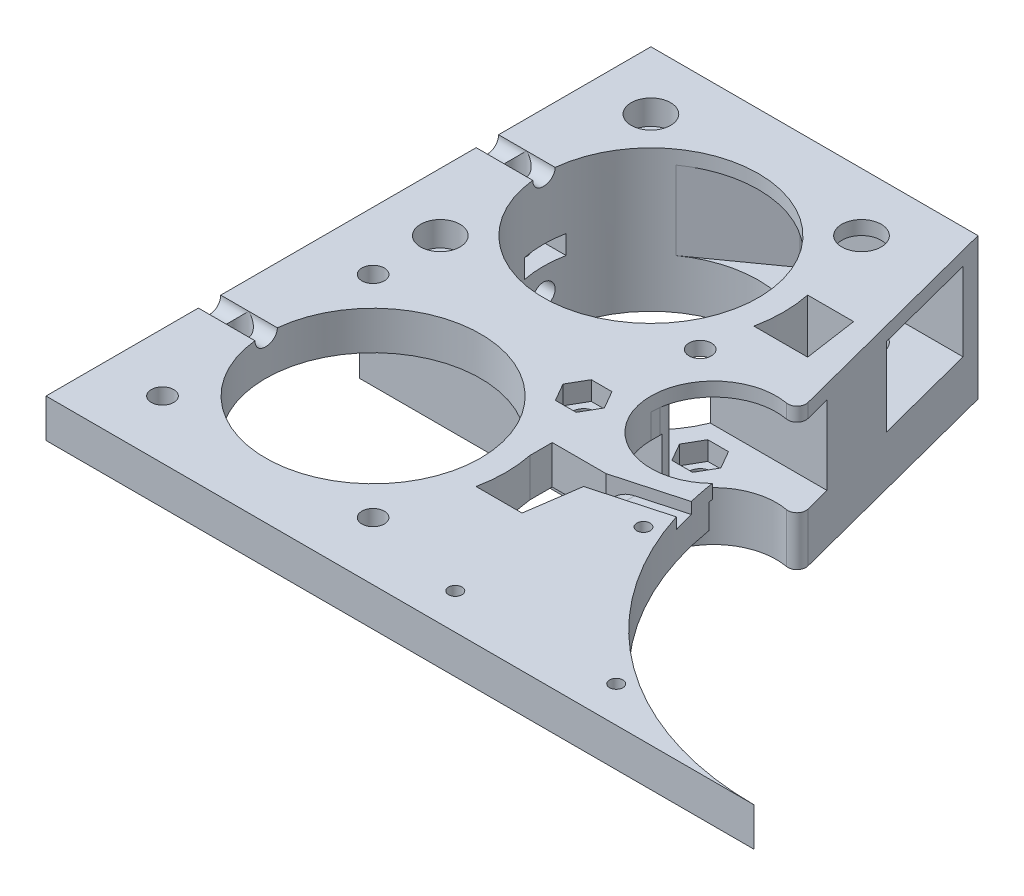
SolidWorks part; units mm, degrees
ref_plane "Alzado" through (0, 0, 0) normal (0, 0, 1) x (1, 0, 0)
ref_plane "Planta" through (0, 0, 0) normal (0, 1, 0) x (1, 0, 0)
ref_plane "Vista lateral" through (0, 0, 0) normal (1, 0, 0) x (0, 0, -1)
sketch "Croquis1" plane through (0, 0, 0) normal (0, 1, 0) x (1, 0, 0)
  line L1 (0, -67.5) -> (-158, -67.5)
  line L3 (0, 67.5) -> (-158, 67.5)
  line L4 (-158, -67.5) -> (-158, 67.5)
  arc A0 (0, -67.5) -> (0, 67.5) centre (0, 0) ccw
  dimension "D2" = 135
  dimension "D1" = 158
extrude "Saliente-Extruir4" add sketch "Croquis1" along normal blind 8.6
sketch "Croquis3" plane through (0, 0, 0) normal (0, -1, 0) x (1, 0, 0)
  line L0 (-85, -67.5) -> (-68.1481, -2.5)
  line L1 (-71.4961, -15.4136) -> (-68.1506, -2.5096) construction
  line L3 (-68.1481, -2.5) -> (-158, -2.5)
  line L4 (-158, -2.5) -> (-158, -67.5)
  line L5 (-158, -67.5) -> (-85, -67.5)
extrude "Saliente-Extruir2" add sketch "Croquis3" along normal up to surface (23 mm away)
sketch "Croquis2" plane through (0, 0, 0) normal (0, 1, 0) x (1, 0, 0)
  line L0 (-17.38, 0) -> (17.38, 0) construction
  circle A0 centre (-76.5, 0) radius 14
  circle A2 centre (-121.5, 31) radius 24
  circle A3 centre (-121.5, -31) radius 24
  dimension "D1" = 28
  dimension "D2" = 48
extrude "Cortar-Extruir1" cut sketch "Croquis2" along normal through all both and the other way through all
sketch "Croquis5" plane through (0, 8.6, 0) normal (0, 1, 0) x (1, 0, 0)
  line L1 (-145, -54.5) -> (-98, -54.5) construction
  line L2 (-145, -54.5) -> (-145, -7.5) construction
  line L3 (-145, -7.5) -> (-98, -7.5) construction
  line L4 (-98, -54.5) -> (-98, -7.5) construction
  circle A0 centre (-145, -7.5) radius 2.5
  circle A1 centre (-145, -54.5) radius 2.5
  circle A2 centre (-98, -54.5) radius 2.5
  circle A3 centre (-98, -7.5) radius 2.5
  circle A4 centre (-145, 7.5) radius 2.5
  circle A5 centre (-145, 54.5) radius 2.5
  dimension "D1" = 5
extrude "Cortar-Extruir2" cut sketch "Croquis5" against normal through all
sketch "Croquis6" plane through (0, 8.6, 0) normal (0, 1, 0) x (1, 0, 0)
  line L0 (0, -67.5) -> (-85, -67.5)
  line L1 (-85, -67.5) -> (-70.8172, -12.7947)
  line L2 (0, 67.5) -> (-85, 67.5)
  line L3 (-85, 67.5) -> (-70.8172, 12.7947)
  line L4 (0, 67.5) -> (-158, 67.5) construction
  arc A1 (0, -67.5) -> (0, 67.5) centre (0, 0) ccw
  arc A3 (-70.8172, -12.7947) -> (-70.8172, 12.7947) centre (-76.5, 0) ccw
  circle A4 centre (-76.5, 0) radius 14 construction
  arc A5 (0, -67.5) -> (0, 67.5) centre (0, 0) ccw construction
extrude "Saliente-Extruir3" add sketch "Croquis6" against normal blind 15.6
sketch "Croquis7" plane through (0, 0, 0) normal (0, 1, 0) x (1, 0, 0)
  circle A0 centre (0, 0) radius 6
  dimension "D1" = 12
extrude "Cortar-Extruir3" cut sketch "Croquis7" against normal through all both and the other way through all
sketch "Croquis8" plane through (0, -7, 0) normal (0, -1, 0) x (1, 0, 0)
  line L0 (0, -63) -> (-116.397, -63)
  line L1 (-119.3042, -62.068) -> (-135.4544, -50.5263)
  line L2 (-158, -67.5) -> (-158, -2.5) construction
  line L3 (-121.5, -7) -> (-95.5, -7)
  line L4 (-90.5, -2) -> (-90.5, 0)
  arc A0 (0, -63) -> (-61.2515, 14.7395) centre (0, 0) ccw
  circle A1 centre (-121.5, -31) radius 24 construction
  arc A2 (-121.5, -7) -> (-135.4544, -50.5263) centre (-121.5, -31) ccw
  arc A4 (-70.8172, 12.7947) -> (-90.275, -2.5) centre (-76.5, 0) ccw construction
  arc A7 (-70.8172, 12.7947) -> (-90.5, 0) centre (-76.5, 0) ccw
  arc A10 (-70.8172, -12.7947) -> (-70.8172, 12.7947) centre (-76.5, 0) ccw construction
  arc A11 (-68.8462, 11.7226) -> (-70.8172, 12.7947) centre (-76.5, 0) ccw
  arc A12 (-61.2515, 14.7395) -> (-68.8462, 11.7226) centre (-66.1127, 15.9093) cw
  arc A13 (-90.5, -2) -> (-95.5, -7) centre (-95.5, -2) cw
  arc A14 (-116.397, -63) -> (-119.3042, -62.068) centre (-116.397, -58) cw
  point P27 (-118, -63)
  dimension "D1" = 126
  dimension "D3" = 5
  dimension "D4" = 5
  dimension "D5" = 5
  dimension "D2" = 40
extrude "Cortar-Extruir4" cut sketch "Croquis8" against normal blind 12.5 and the other way blind 5 body kept at (0, 8.6, 67.5)
fillet "Redondeo1" radius 2 1 edges at (-70.8172, -17.5, -12.7947)
sketch "Croquis9" plane through (0, 5.5, 0) normal (0, -1, 0) x (1, 0, 0)
  circle A0 centre (0, 0) radius 6 construction
  circle A1 centre (0, 0) radius 6
  circle A2 centre (0, 0) radius 16.85
  dimension "D1" = 33.7
extrude "Saliente-Extruir5" add sketch "Croquis9" along normal blind 4.65
sketch "Croquis10" plane through (0, 0.85, 0) normal (0, -1, 0) x (1, 0, 0)
  circle A0 centre (0, 0) radius 6 construction
  circle A1 centre (0, 0) radius 6
  circle A2 centre (0, 0) radius 10
  dimension "D1" = 20
extrude "Saliente-Extruir6" add sketch "Croquis10" along normal blind 29
fillet "Redondeo2" radius 0.5 1 edges at (0, 0.85, -16.85)
fillet "Redondeo3" radius 2 1 edges at (0, 5.5, -16.85)
sketch "Croquis11" plane through (0, 5.5, 0) normal (0, -1, 0) x (1, 0, 0)
  line L0 (-121.5, -31) -> (-75.537, -31) construction
  line L1 (-71.7118, -16.2457) -> (-85, -67.5) construction
  line L2 (-73.2037, -22) -> (-77.8704, -40)
  line L3 (-99.2514, -22) -> (-73.2037, -22)
  line L4 (-99.2514, -40) -> (-77.8704, -40)
  circle A0 centre (-121.5, -31) radius 24 construction
  arc A1 (-99.2514, -40) -> (-99.2514, -22) centre (-121.5, -31) ccw
  dimension "D1" = 9
extrude "Saliente-Extruir7" add sketch "Croquis11" along normal up to next
sketch "Croquis12" plane through (0, -7, 0) normal (0, -1, 0) x (1, 0, 0)
  line L2 (-63.0732, 14.8024) -> (-77.256, 69.5077)
  line L3 (-63.0732, 14.8024) -> (-77.256, 69.5077) construction
  line L4 (17.38, 0) -> (-17.38, 0) construction
  line L5 (-85, 59.5) -> (0, 59.5)
  line L6 (-85, 59.5) -> (0, 59.5) construction
  circle A0 centre (0, 0) radius 71 construction
  circle A2 centre (-74.6614, 59.5) radius 1.5
  circle A3 centre (-66.0127, 26.1405) radius 1.5
  circle A4 centre (-38.7395, 59.5) radius 1.5
  circle A5 centre (-38.7395, -59.5) radius 1.5
  circle A6 centre (-74.6614, -59.5) radius 1.5
  circle A7 centre (-66.0127, -26.1405) radius 1.5
  circle A8 centre (0, 0) radius 67.5 construction
  arc A9 (0, -67.5) -> (0, 67.5) centre (0, 0) ccw construction
  dimension "D1" = 142
  dimension "D4" = 3
  dimension "D2" = 8
  dimension "D3" = 8
extrude "Cortar-Extruir5" cut sketch "Croquis12" against normal through all
sketch "Croquis13" plane through (0, 5.5, 0) normal (0, -1, 0) x (1, 0, 0)
  line L1 (-70.9087, -59.5) -> (-72.785, -56.25)
  line L2 (-72.785, -56.25) -> (-76.5378, -56.25)
  line L3 (-76.5378, -56.25) -> (-78.4142, -59.5)
  line L4 (-78.4142, -59.5) -> (-76.5378, -62.75)
  line L5 (-76.5378, -62.75) -> (-72.785, -62.75)
  line L6 (-72.785, -62.75) -> (-70.9087, -59.5)
  line L7 (-62.2599, -26.1405) -> (-64.1363, -22.8905)
  line L8 (-64.1363, -22.8905) -> (-67.8891, -22.8905)
  line L9 (-67.8891, -22.8905) -> (-69.7655, -26.1405)
  line L10 (-69.7655, -26.1405) -> (-67.8891, -29.3905)
  line L11 (-67.8891, -29.3905) -> (-64.1363, -29.3905)
  line L12 (-64.1363, -29.3905) -> (-62.2599, -26.1405)
  line L13 (-34.9867, -59.5) -> (-36.8631, -56.25)
  line L14 (-36.8631, -56.25) -> (-40.6159, -56.25)
  line L15 (-40.6159, -56.25) -> (-42.4923, -59.5)
  line L16 (-42.4923, -59.5) -> (-40.6159, -62.75)
  line L17 (-40.6159, -62.75) -> (-36.8631, -62.75)
  line L18 (-36.8631, -62.75) -> (-34.9867, -59.5)
  circle A0 centre (-74.6614, -59.5) radius 3.25 construction
  circle A1 centre (-66.0127, -26.1405) radius 3.25 construction
  circle A2 centre (-38.7395, -59.5) radius 3.25 construction
  dimension "D1" = 6.5
extrude "Cortar-Extruir6" cut sketch "Croquis13" against normal blind 2
sketch "Croquis14" plane through (0, -7, 0) normal (0, -1, 0) x (1, 0, 0)
  circle A0 centre (-66.0127, 26.1405) radius 3
  circle A1 centre (-74.6614, 59.5) radius 3
  circle A2 centre (-38.7395, 59.5) radius 3
  dimension "D1" = 6
extrude "Cortar-Extruir7" cut sketch "Croquis14" against normal blind 3.7
sketch "Croquis15" plane through (0, -23, 0) normal (0, -1, 0) x (1, 0, 0)
  line L0 (-71.7118, -16.2457) -> (-85, -67.5) construction
  line L1 (-97.5, -31) -> (-75.537, -31) construction
  line L2 (17.38, 0) -> (-17.38, 0) construction
  circle A0 centre (-121.5, -31) radius 24 construction
  circle A1 centre (-86.5185, -31) radius 2
  circle A2 centre (-86.5185, 31) radius 2
  dimension "D1" = 4
extrude "Cortar-Extruir8" [suppressed] cut sketch "Croquis15" against normal through all
sketch "Croquis16" [suppressed] plane through (0, 0, 0) normal (0, -1, 0) x (1, 0, 0)
  circle A0 centre (-86.5185, 31) radius 4
  dimension "D1" = 8
extrude "Cortar-Extruir9" [suppressed] cut sketch "Croquis16" against normal blind 4
sketch "Croquis17" [suppressed] plane through (0, -23, 0) normal (0, -1, 0) x (1, 0, 0)
  line L1 (-82.1884, -31) -> (-84.3535, -27.25)
  line L2 (-84.3535, -27.25) -> (-88.6836, -27.25)
  line L3 (-88.6836, -27.25) -> (-90.8486, -31)
  line L4 (-90.8486, -31) -> (-88.6836, -34.75)
  line L5 (-88.6836, -34.75) -> (-84.3535, -34.75)
  line L6 (-84.3535, -34.75) -> (-82.1884, -31)
  circle A0 centre (-86.5185, -31) radius 3.75 construction
  dimension "D1" = 7.5
extrude "Cortar-Extruir10" [suppressed] cut sketch "Croquis17" against normal blind 10
sketch "Croquis19" plane through (0, 8.6, 0) normal (0, 1, 0) x (1, 0, 0)
  line L0 (0, -17.38) -> (0, 17.38) construction
  line L1 (-158, -67.5) -> (0, -67.5) construction
  line L2 (-52.483, -17.2558) -> (-40.4717, -33.0039)
  line L3 (-55.6329, -13.1259) -> (-51.6573, -10.0936)
  line L4 (-40.4717, -33.0039) -> (-36.4961, -29.9717)
  line L5 (-51.6573, -10.0936) -> (-36.4961, -29.9717)
  line L6 (-55.6329, -13.1259) -> (-36.4961, -29.9717) construction
  line L7 (-40.4717, -33.0039) -> (-51.6573, -10.0936) construction
  line L8 (-40, -29.5) -> (-62.5, 0) construction
  line L9 (-17.38, 0) -> (17.38, 0) construction
  line L10 (-80.5185, -20) -> (-55.6329, -13.1259)
  line L11 (-92.5185, -25) -> (-80.5185, -25)
  line L12 (-92.5185, -25) -> (-92.5185, -20)
  line L13 (-92.5185, -20) -> (-80.5185, -20)
  line L15 (-92.5185, -25) -> (-80.5185, -20) construction
  line L16 (-92.5185, -20) -> (-80.5185, -25) construction
  line L17 (-80.5185, -25) -> (-52.483, -17.2558)
  circle A0 centre (-40, -29.5) radius 2.5 construction
  circle A1 centre (-76.5, 0) radius 14 construction
  circle A3 centre (-86.5185, -31) radius 2 construction
  point P7 (-46.0645, -21.5488)
  point P19 (-86.5185, -22.5)
  dimension "D1" = 5
  dimension "D2" = 40
  dimension "D3" = 38
  dimension "D4" = 25
  dimension "D5" = 5
  dimension "D6" = 12
  dimension "D7" = 20
  dimension "D8" = 16.0185
  dimension "D9" = 28.0355
  dimension "D10" = 7.7442
extrude "Cortar-Extruir11" cut sketch "Croquis19" against normal blind 2.5
sketch "Croquis20" plane through (0, 8.6, 0) normal (0, 1, 0) x (1, 0, 0)
  line L0 (-80.5185, -20) -> (-92.5185, -20) construction
  line L1 (-92.5185, -25) -> (-80.5185, -25)
  line L2 (-92.5185, -25) -> (-92.5185, -20)
  line L3 (-92.5185, -20) -> (-80.5185, -20)
  line L4 (-80.5185, -25) -> (-80.5185, -20)
  line L5 (-92.5185, -25) -> (-80.5185, -20) construction
  line L6 (-92.5185, -20) -> (-80.5185, -25) construction
  line L7 (-92.5185, -20) -> (-92.5185, -25) construction
  line L8 (-92.5185, -25) -> (-80.5185, -25) construction
  point P0 (-86.5185, -22.5)
extrude "Cortar-Extruir12" cut sketch "Croquis20" against normal through all
fillet "Redondeo4" radius 5 1 edges at (-80.5185, 6.1, 22.5)
sketch "Croquis21" plane through (0, 8.6, 0) normal (0, 1, 0) x (1, 0, 0)
  line L0 (-158, 67.5) -> (-158, -67.5) construction
  line L1 (-158, 67.5) -> (-158, -67.5)
  line L2 (-158, 67.5) -> (-85, 67.5)
  line L4 (-158, -67.5) -> (0, -67.5)
  line L5 (-73.2037, 22) -> (-71.7118, 16.2457) construction
  line L6 (-77.8704, 40) -> (-73.2037, 22) construction
  line L7 (-83.8333, 63) -> (-77.8704, 40) construction
  line L8 (-85, 67.5) -> (-83.8333, 63) construction
  line L10 (-73.2037, 22) -> (-71.7118, 16.2457)
  line L11 (-77.8704, 40) -> (-73.2037, 22)
  line L12 (-83.8333, 63) -> (-77.8704, 40)
  line L13 (-85, 67.5) -> (-83.8333, 63)
  circle A0 centre (-76.5, 0) radius 14 construction
  arc A1 (-74.0044, 13.7758) -> (-71.7118, 16.2457) centre (-73.6478, 15.7437) ccw construction
  arc A2 (-74.0044, 13.7758) -> (-66.7484, -10.0452) centre (-76.5, 0) ccw
  arc A3 (-74.0044, 13.7758) -> (-71.7118, 16.2457) centre (-73.6478, 15.7437) ccw
  arc A4 (-66.7484, -10.0452) -> (0, -67.5) centre (0, 0) ccw
  arc A6 (0, -67.5) -> (0, 67.5) centre (0, 0) ccw construction
extrude "Cortar-Extruir13" cut sketch "Croquis21" against normal through all and the other way through all flip side to cut
sketch "Croquis22" plane through (0, -7, 0) normal (0, -1, 0) x (1, 0, 0)
  line L1 (-70.8172, 12.7947) -> (-85, 67.5) construction
  line L3 (-70.8172, 12.7947) -> (-85, 67.5)
  spline S0 degree 3 poles (-85, 67.5) (12.8062, 155.3204) (41.7318, 17.3202) (-80.1747, -16.0938) (-70.8172, 12.7947) knots 0 0 0 0 0.745808 1 1 1 1
extrude "Cortar-Extruir14" cut sketch "Croquis22" against normal up to surface (7 mm away) up to face at (-86.5185, 0, 22.5)
sketch "Croquis24" plane through (0, 8.6, 0) normal (0, 1, 0) x (1, 0, 0)
  line L0 (-82.2579, 37) -> (-80.5185, 25)
  line L1 (-82.2579, 37) -> (-92.5185, 37)
  line L2 (-80.5185, 25) -> (-92.5185, 25)
  line L4 (-99.2514, 40) -> (-77.8704, 40) construction
  line L6 (-17.38, 0) -> (17.38, 0) construction
  line L7 (-80.5185, -25) -> (-92.5185, -25)
  line L8 (-82.2579, -37) -> (-92.5185, -37)
  line L9 (-82.2579, -37) -> (-80.5185, -25)
  line L10 (-92.5185, -25) -> (-80.5185, -25) construction
  line L11 (-92.5185, -20) -> (-92.5185, -25) construction
  line L12 (-80.5185, -25) -> (-80.5185, -20) construction
  line L13 (-71.7118, 16.2457) -> (-85, 67.5) construction
  arc A1 (-92.5185, -25) -> (-92.5185, -37) centre (-121.5, -31) cw
  circle A2 centre (-121.5, 31) radius 24 construction
  arc A3 (-92.5185, 25) -> (-92.5185, 37) centre (-121.5, 31) ccw
  point P10 (-86.5185, -25)
  dimension "D3" = 3
  dimension "D1" = 5
extrude "Cortar-Extruir15" cut sketch "Croquis24" against normal through all both and the other way through all
sketch "Croquis25" plane through (0, 8.6, 0) normal (0, 1, 0) x (1, 0, 0)
  circle A0 centre (-145, 54.5) radius 4.4
  circle A1 centre (-145, 7.5) radius 4.4
  dimension "D1" = 8.8
extrude "Cortar-Extruir16" cut sketch "Croquis25" against normal blind 5.5
sketch "Croquis26" plane through (0, -23, 0) normal (0, -1, 0) x (1, 0, 0)
  circle A0 centre (-145, -54.5) radius 4.4 construction
  circle A1 centre (-145, -7.5) radius 4.4 construction
  circle A2 centre (-145, -54.5) radius 4.4
  circle A3 centre (-145, -7.5) radius 4.4
extrude "Cortar-Extruir17" cut sketch "Croquis26" against normal blind 5.5
sketch "Croquis27" plane through (0, 8.6, 0) normal (0, 1, 0) x (1, 0, 0)
  line L0 (-121.5, 31) -> (-121.5, -31) construction
  circle A1 centre (-145, 54.5) radius 2.5 construction
  circle A3 centre (-145, 54.5) radius 2.5 construction
  circle A4 centre (-98, 54.5) radius 2.5
extrude "Cortar-Extruir18" cut sketch "Croquis27" against normal through all
sketch "Croquis28" plane through (0, -12, 0) normal (0, 1, 0) x (1, 0, 0)
  circle A0 centre (-98, 54.5) radius 4.4
  circle A1 centre (-145, 54.5) radius 4.4 construction
extrude "Cortar-Extruir19" cut sketch "Croquis28" against normal blind 5.5 and the other way through all
ref_plane "Plano1" through (0, -7.2, 0) normal (0, -1, 0) x (-1, 0, 0)
sketch "Croquis29" plane through (0, -7.2, 0) normal (0, -1, 0) x (-1, 0, 0)
  line L0 (145.5, 31) -> (158, 31) construction
  line L1 (158, 67.5) -> (158, 2.5) construction
  line L2 (-17.38, 0) -> (17.38, 0) construction
  line L3 (94, 22) -> (94, 7) construction
  line L4 (73.2037, 22) -> (99.2514, 22) construction
  line L5 (95.5, 7) -> (121.5, 7) construction
  circle A0 centre (121.5, 31) radius 24 construction
  circle A1 centre (151.75, 31) radius 2.5
  circle A2 centre (151.75, -31) radius 2.5
  circle A5 centre (94, 14.5) radius 2.5
  point P21 (94, 14.5)
  dimension "D1" = 5
  dimension "D2" = 64
extrude "Cortar-Extruir20" cut sketch "Croquis29" against normal through all both and the other way through all
sketch "Croquis30" plane through (0, -7.2, 0) normal (0, -1, 0) x (-1, 0, 0)
  line L0 (151.75, 35.6188) -> (145.0514, 35.6188)
  line L1 (151.75, 26.3812) -> (155.75, 28.6906)
  line L2 (155.75, 28.6906) -> (155.75, 33.3094)
  line L3 (155.75, 33.3094) -> (151.75, 35.6188)
  line L7 (151.75, 26.3812) -> (145.0514, 26.3812)
  line L9 (147.75, 28.6906) -> (151.75, 26.3812) [skipped]
  line L10 (147.75, 33.3094) -> (147.75, 28.6906) [skipped]
  line L11 (151.75, 35.6188) -> (147.75, 33.3094) [skipped]
  circle A0 centre (151.75, 31) radius 4 construction
  circle A1 centre (121.5, 31) radius 24 construction
  arc A2 (145.0514, 26.3812) -> (145.0514, 35.6188) centre (121.5, 31) ccw
  circle A3 centre (151.75, 31) radius 2.5 construction
  dimension "D1" = 8
extrude "Cortar-Extruir21" cut sketch "Croquis30" against normal mid plane 4.25
sketch "Croquis31" plane through (-158, 0, 0) normal (-1, 0, 0) x (0, 0, 1)
  line L1 (28.5, 8.6) -> (33.5, 8.6) construction
  line L3 (-67.5, 8.6) -> (67.5, 8.6) construction
  circle A0 centre (31, 8.6) radius 2.5
  point P4 (31, 8.6)
  dimension "D1" = 5
extrude "Cortar-Extruir23" cut sketch "Croquis31" against normal up to surface (12.6306 mm away) up to face at (-121.5, 8.6, 55)
ref_plane "Plano2" through (-82.2579, -23, -37) normal (0, 1, 0) x (1, 0, 0)
sketch "Croquis33" plane through (-158, 0, 0) normal (-1, 0, 0) x (0, 0, 1)
  line L0 (-33.5, 8.6) -> (-28.5, 8.6) construction
  circle A0 centre (-31, 8.6) radius 2.5
  point P7 (-31, 8.6)
  dimension "D1" = 5
extrude "Cortar-Extruir24" cut sketch "Croquis33" against normal up to surface (12.6306 mm away) up to face at (-116.0761, -3.25, -49.6544)
sketch "Croquis34" plane through (-158, 0, 0) normal (-1, 0, 0) x (0, 0, 1)
  line L0 (-31, 8.6) -> (-31, -23) construction
  line L4 (-7, 8.6) -> (-55, 8.6) construction
  line L5 (-28.31, -23) -> (-45.69, -23) construction
  line L6 (-28.5, 8.6) -> (28.5, 8.6) construction
  circle A0 centre (-31, -14.9) radius 2.5
  dimension "D1" = 5
  dimension "D2" = 23.5
extrude "Cortar-Extruir25" cut sketch "Croquis34" against normal up to surface (12.6306 mm away) up to face at (-121.4968, 9.8189, -30.7229)
sketch "Croquis35" plane through (0, -12, 0) normal (0, 1, 0) x (1, 0, 0)
  line L1 (-89.3812, 14.5) -> (-91.6906, 18.5)
  line L2 (-91.6906, 18.5) -> (-96.3094, 18.5)
  line L3 (-96.3094, 18.5) -> (-98.6188, 14.5)
  line L4 (-98.6188, 14.5) -> (-96.3094, 10.5)
  line L5 (-96.3094, 10.5) -> (-91.6906, 10.5)
  line L6 (-91.6906, 10.5) -> (-89.3812, 14.5)
  circle A0 centre (-94, 14.5) radius 4 construction
  dimension "D1" = 8
extrude "Cortar-Extruir26" cut sketch "Croquis35" against normal blind 4.2
sketch "Croquis36" plane through (0, 8.6, 0) normal (0, 1, 0) x (1, 0, 0)
  line L1 (-93.3812, -7.5) -> (-95.6906, -3.5)
  line L2 (-95.6906, -3.5) -> (-100.3094, -3.5)
  line L3 (-100.3094, -3.5) -> (-102.6188, -7.5)
  line L4 (-102.6188, -7.5) -> (-100.3094, -11.5)
  line L5 (-100.3094, -11.5) -> (-95.6906, -11.5)
  line L6 (-95.6906, -11.5) -> (-93.3812, -7.5)
  circle A0 centre (-98, -7.5) radius 4 construction
  dimension "D1" = 8
extrude "Cortar-Extruir27" cut sketch "Croquis36" against normal blind 4.2
